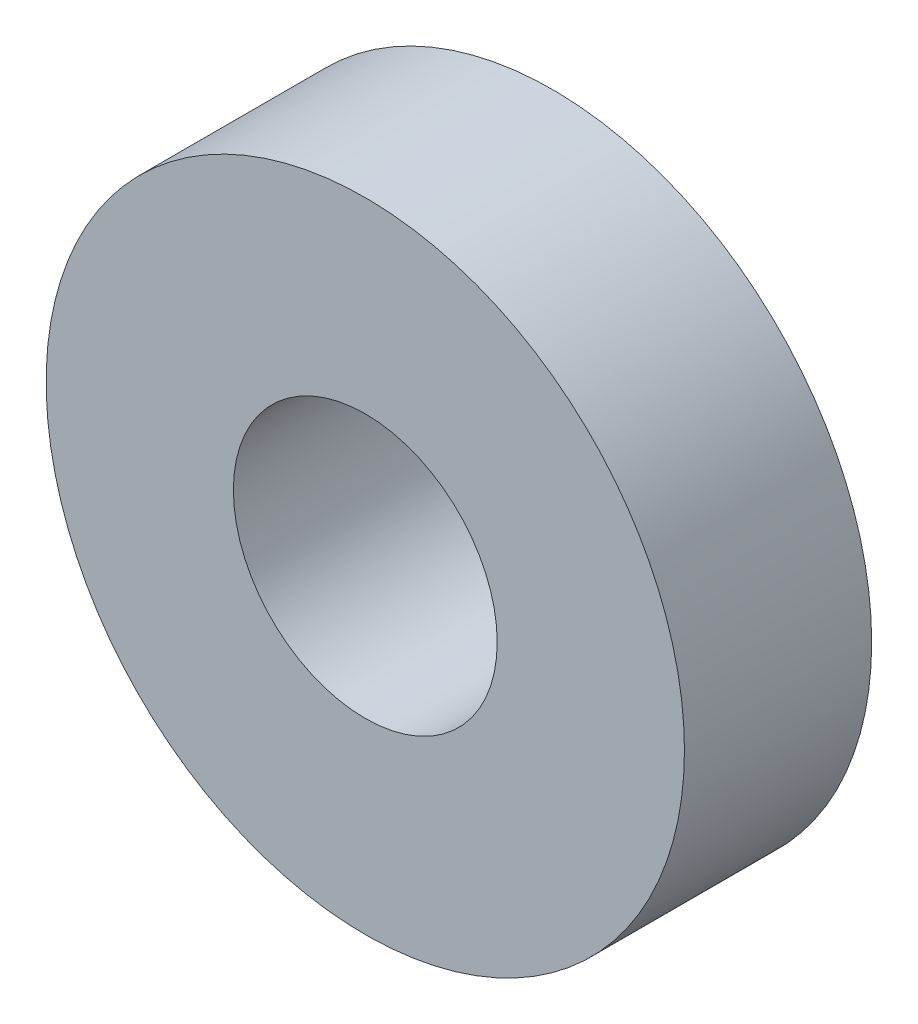
SolidWorks part; units mm, degrees
ref_plane "Front Plane" through (0, 0, 0) normal (0, 0, 1) x (1, 0, 0)
ref_plane "Top Plane" through (0, 0, 0) normal (0, 1, 0) x (1, 0, 0)
ref_plane "Right Plane" through (0, 0, 0) normal (1, 0, 0) x (0, 0, -1)
sketch "Sketch1" plane through (0, 0, 0) normal (1, 0, 0) x (0, 0, -1)
  line L0 (0, 9.525) -> (0, 3.937)
  line L1 (0, 3.937) -> (5.588, 3.937)
  line L2 (5.588, 3.937) -> (5.588, 9.525)
  line L3 (5.588, 9.525) -> (0, 9.525)
  line L4 (5.588, 0) -> (0, 0) construction
revolve "Revolve1" add sketch "Sketch1" angle 360 about L4 reverse direction yes
ref_plane "part to rod XY" through (0, 0, 0) normal (0, 0, 1) x (1, 0, 0)
ref_plane "part to rod XZ" through (0, 0, 0) normal (0, -1, 0) x (-1, 0, 0)
ref_plane "part to rod YZ" through (0, 0, 0) normal (1, 0, 0) x (0, 0, -1)
ref_axis "part to rod X" through (-80.9, 0, 0) along (1, 0, 0)
ref_axis "part to rod Y" through (0, -50, 0) along (0, 1, 0)
ref_axis "part to rod Z" through (0, 0, 80.9) along (0, 0, -1)
sketch3d "part to rod"
  point P0 (0, 0, 0)
